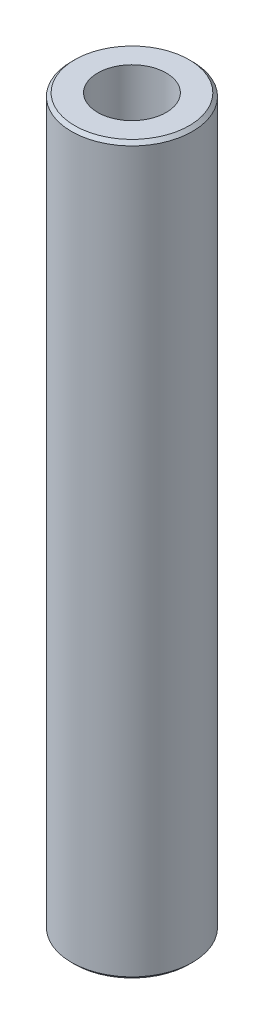
SolidWorks part; units mm, degrees
ref_plane "Front Plane" through (0, 0, 0) normal (0, 0, 1) x (1, 0, 0)
ref_plane "Top Plane" through (0, 0, 0) normal (0, 1, 0) x (1, 0, 0)
ref_plane "Right Plane" through (0, 0, 0) normal (1, 0, 0) x (0, 0, -1)
sketch "Sketch1" plane through (0, 0, 0) normal (0, 1, 0) x (1, 0, 0)
  circle A0 centre (0, 0) radius 50
  dimension "SHAFT_OD" = 100
extrude "Boss-Extrude1" add sketch "Sketch1" along normal blind 600
sketch "Sketch2" plane through (0, 0, 0) normal (0, 1, 0) x (1, 0, 0)
  circle A0 centre (0, 0) radius 28.301
  dimension "BORE_D" = 56.6021
extrude "Cut-Extrude1" cut sketch "Sketch2" along normal through all
chamfer "Chamfer1" distance 2.7413 angle 45 2 edges at (0, 600, 50) (0, 0, 50)
